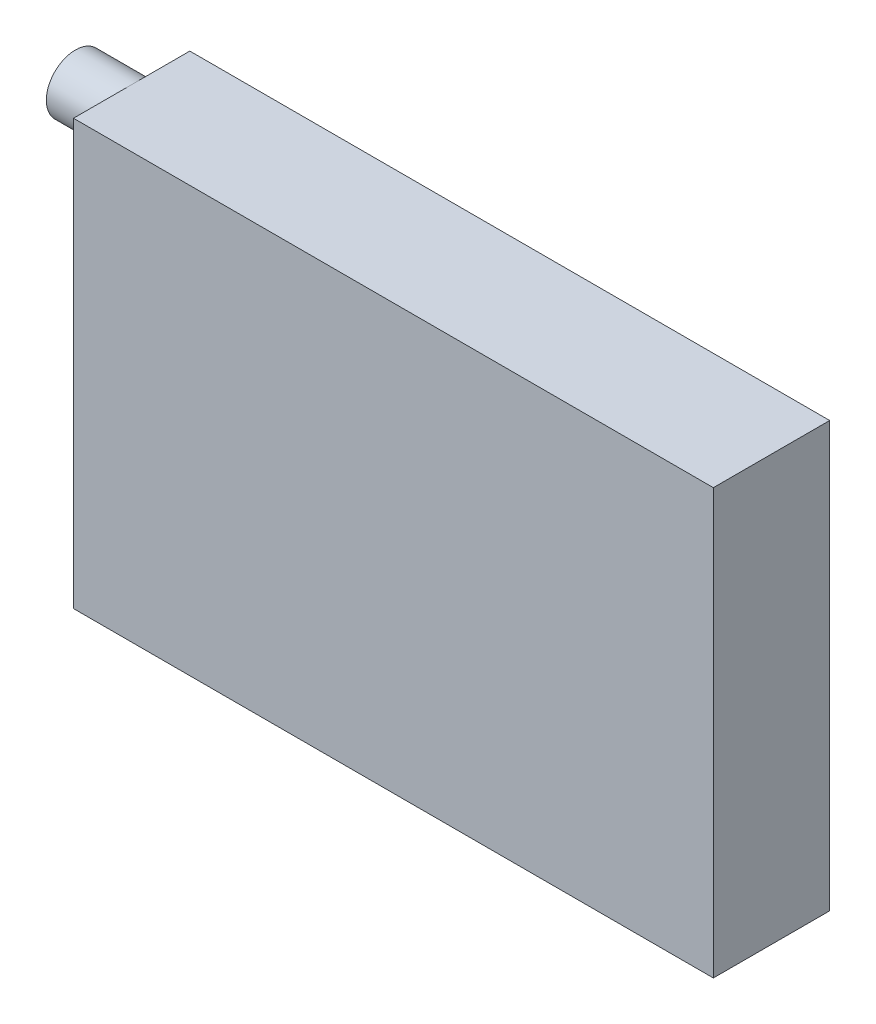
SolidWorks part; units mm, degrees
ref_plane "前视基准面" through (0, 0, 0) normal (0, 0, 1) x (1, 0, 0)
ref_plane "上视基准面" through (0, 0, 0) normal (0, 1, 0) x (1, 0, 0)
ref_plane "右视基准面" through (0, 0, 0) normal (1, 0, 0) x (0, 0, -1)
other "Configuration Table"
sketch "草图1" plane through (0, 0, 0) normal (0, 0, 1) x (1, 0, 0)
  line L1 (-55, 36.5) -> (55, 36.5)
  line L2 (-55, 36.5) -> (-55, -36.5)
  line L3 (-55, -36.5) -> (55, -36.5)
  line L4 (55, 36.5) -> (55, -36.5)
  line L5 (-55, 36.5) -> (55, -36.5) construction
  line L6 (-55, -36.5) -> (55, 36.5) construction
  point P0 (0, 0)
  dimension "D1" = 73
  dimension "D2" = 110
extrude "凸台-拉伸1" add sketch "草图1" along normal blind 20
sketch "草图2" plane through (-55, 0, 0) normal (-1, 0, 0) x (0, 0, 1)
  line L0 (20, 36.5) -> (0, 36.5) construction
  circle A0 centre (9.6692, 31.5) radius 5
  dimension "D1" = 5
extrude "凸台-拉伸2" add sketch "草图2" along normal blind 10
